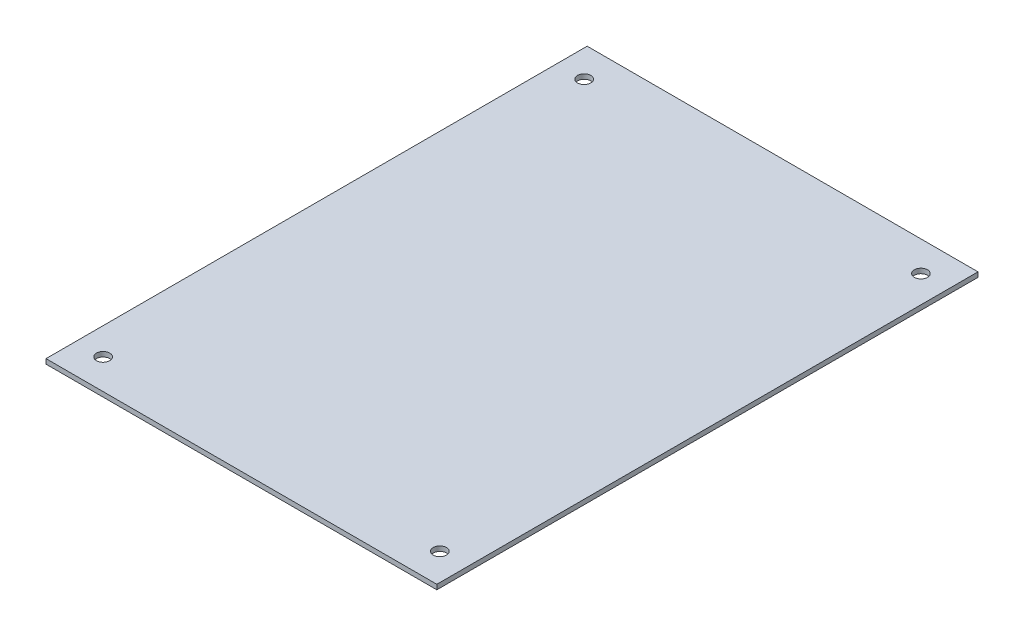
SolidWorks part; units mm, degrees
ref_plane "Front Plane" through (0, 0, 0) normal (0, 0, 1) x (1, 0, 0)
ref_plane "Top Plane" through (0, 0, 0) normal (0, 1, 0) x (1, 0, 0)
ref_plane "Right Plane" through (0, 0, 0) normal (1, 0, 0) x (0, 0, -1)
sketch "Sketch1" plane through (0, 0, 0) normal (0, 1, 0) x (1, 0, 0)
  line L0 (32.5, 0) -> (32.5, -13.3553)
  line L1 (0, 0) -> (65, 0)
  line L2 (0, 0) -> (0, 90)
  line L3 (0, 90) -> (65, 90)
  line L4 (65, 0) -> (65, 90)
  line L5 (0, 45) -> (-12.7347, 45)
  circle A0 centre (4.5, 5) radius 1.1
  circle A4 centre (4.5, 85) radius 1.1
  circle A5 centre (60.5, 5) radius 1.1
  circle A6 centre (60.5, 85) radius 1.1
  point P4 (32.5, 0)
  point P5 (0, 45)
  dimension "D3" = 2.2
  dimension "D4" = 28
  dimension "D1" = 90
  dimension "D2" = 65
  dimension "D5" = 40
extrude "Boss-Extrude1" add sketch "Sketch1" along normal blind 0.8 contours L1 L4 L3 L2 A6 A4 A0 A5 region at (32.5, 0, -45)
